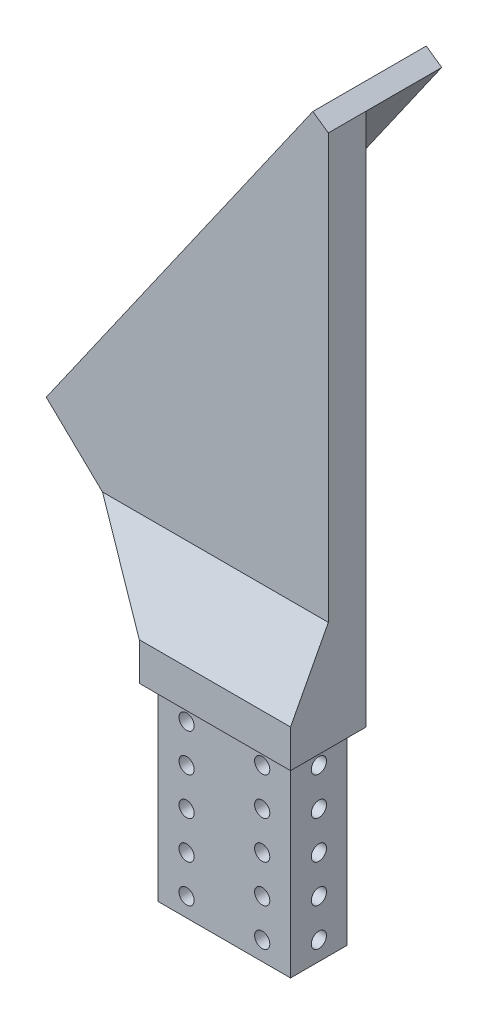
SolidWorks part; units mm, degrees
material "6061-T6 (SS)"
ref_plane "Front Plane" through (0, 0, 0) normal (0, 0, 1) x (1, 0, 0)
ref_plane "Top Plane" through (0, 0, 0) normal (0, 1, 0) x (1, 0, 0)
ref_plane "Right Plane" through (0, 0, 0) normal (1, 0, 0) x (0, 0, -1)
sketch "Sketch1" plane through (0, 0, 0) normal (0, 0, 1) x (1, 0, 0)
  line L0 (50.8, 76.2) -> (152.4, 76.2)
  line L1 (0, 0) -> (50.8, 0)
  line L2 (0, 0) -> (0, 76.2)
  line L4 (50.8, 0) -> (50.8, 76.2)
  line L5 (-101.6, 76.2) -> (0, 76.2)
  line L6 (-101.6, 76.2) -> (-101.6, 254)
  line L7 (-101.6, 254) -> (152.4, 254)
  line L8 (152.4, 76.2) -> (152.4, 254)
  dimension "D1" = 50.8
  dimension "D2" = 76.2
  dimension "D3" = 254
  dimension "D4" = 177.8
extrude "Boss-Extrude1" add sketch "Sketch1" along normal blind 25.4
sketch "Sketch3" plane through (0, 0, 25.4) normal (0, 0, 1) x (1, 0, 0)
  line L0 (50.8, 0) -> (50.8, 76.2) construction
  line L1 (0, 0) -> (50.8, 0)
  line L2 (0, 0) -> (0, 63.5)
  line L3 (0, 63.5) -> (50.8, 63.5)
  line L4 (50.8, 0) -> (50.8, 63.5)
  dimension "D1" = 63.5
sketch "Sketch4" plane through (0, 0, 0) normal (-1, 0, 0) x (0, 0, 1)
  line L0 (25.4, 0) -> (25.4, 63.5) construction
  line L1 (0, 0) -> (25.4, 0)
  line L2 (0, 0) -> (0, 63.5)
  line L3 (0, 63.5) -> (25.4, 63.5)
  line L4 (25.4, 0) -> (25.4, 63.5)
  dimension "D1" = 63.5
sketch "Sketch5" plane through (0, 0, 0) normal (0, 0, -1) x (-1, 0, 0)
  line L1 (0, 0) -> (-50.8, 0)
  line L2 (0, 0) -> (0, 63.5)
  line L3 (0, 63.5) -> (-50.8, 63.5)
  line L4 (-50.8, 0) -> (-50.8, 63.5)
sketch "Sketch6" plane through (50.8, 0, 0) normal (1, 0, 0) x (0, 0, -1)
  line L1 (0, 0) -> (-25.4, 0)
  line L2 (0, 0) -> (0, 63.5)
  line L3 (0, 63.5) -> (-25.4, 63.5)
  line L4 (-25.4, 0) -> (-25.4, 63.5)
extrude "Cut-Extrude1" cut sketch "Sketch3" against normal blind 3.175
extrude "Cut-Extrude2" cut sketch "Sketch4" against normal blind 3.175
extrude "Cut-Extrude3" cut sketch "Sketch5" against normal blind 3.175
extrude "Cut-Extrude4" cut sketch "Sketch6" against normal blind 3.175
sketch "Sketch7" plane through (0, 0, 25.4) normal (0, 0, 1) x (1, 0, 0)
  line L0 (50.8, 76.2) -> (50.8, 254)
  line L4 (152.4, 254) -> (-101.6, 254) construction
  line L5 (50.8, 76.2) -> (152.4, 76.2)
  line L6 (152.4, 76.2) -> (152.4, 254)
  line L7 (152.4, 254) -> (50.8, 254)
extrude "Cut-Extrude5" cut sketch "Sketch7" against normal through all
sketch "Sketch9" plane through (0, 0, 25.4) normal (0, 0, 1) x (1, 0, 0)
  line L0 (34.6576, 254) -> (50.8, 254)
  line L1 (50.8, 254) -> (-101.6, 254) construction
  line L2 (50.8, 254) -> (50.8, 242.697)
  line L3 (50.8, 242.697) -> (34.6576, 254)
  line L4 (50.8, 63.5) -> (50.8, 254) construction
  dimension "D1" = 11.303
  dimension "D2" = 35
extrude "Cut-Extrude7" cut sketch "Sketch9" against normal through all
sketch "Sketch8" plane through (0, 0, 25.4) normal (0, 0, 1) x (1, 0, 0)
  line L2 (34.6576, 254) -> (-101.6, 254) construction
  line L12 (34.6576, 254) -> (-101.6, 59.4039)
  line L13 (-101.6, 59.4039) -> (-101.6, 254)
  line L14 (-101.6, 254) -> (34.6576, 254)
  dimension "D1" = 55
extrude "Cut-Extrude6" cut sketch "Sketch8" against normal through all
sketch "Sketch10" plane through (0, 0, 25.4) normal (0, 0, 1) x (1, 0, 0)
  line L0 (34.6576, 254) -> (45.5977, 246.3397)
  line L1 (34.6576, 254) -> (50.8, 242.697) construction
  line L2 (45.5977, 246.3397) -> (-84.0298, 61.2124)
  line L4 (-84.0298, 61.2124) -> (-94.9699, 68.8727)
  line L5 (-94.9699, 68.8727) -> (34.6576, 254)
  line L6 (-89.8393, 76.2) -> (34.6576, 254) construction
  dimension "D1" = 13.3553
  dimension "D2" = 13.3553
  dimension "D3" = 225.9987
extrude "Cut-Extrude8" cut sketch "Sketch10" against normal through all
sketch "Sketch11" plane through (0, 0, 22.225) normal (0, 0, 1) x (1, 0, 0)
  line L1 (50.8, 63.5) -> (0, 63.5) construction
  line L2 (47.625, 63.5) -> (3.175, 63.5) construction
  line L3 (3.175, 63.5) -> (3.175, 0) construction
  circle A0 centre (12.7, 57.15) radius 2.5527
  circle A1 centre (12.7, 44.45) radius 2.5527
  circle A2 centre (12.7, 31.75) radius 2.5527
  circle A3 centre (12.7, 19.05) radius 2.5527
  circle A4 centre (12.7, 6.35) radius 2.5527
  circle A5 centre (38.1, 44.45) radius 2.5527
  circle A6 centre (38.1, 31.75) radius 2.5527
  circle A7 centre (38.1, 19.05) radius 2.5527
  circle A8 centre (38.1, 6.35) radius 2.5527
  circle A9 centre (38.1, 57.15) radius 2.5527
  dimension "D1" = 5.1054
  dimension "D2" = 9.525
  dimension "D3" = 6.35
  dimension "D6" = 25.4
  dimension "D7" = 12.7
  dimension "D8" = 6.35
  dimension "D4" = 5
  dimension "D5" = 2
sketch "Sketch12" plane through (3.175, 0, 0) normal (-1, 0, 0) x (0, 0, 1)
  line L0 (0, 63.5) -> (25.4, 63.5) construction
  line L2 (3.175, 0) -> (3.175, 63.5) construction
  circle A0 centre (12.7, 57.15) radius 2.5527
  circle A1 centre (12.7, 44.45) radius 2.5527
  circle A2 centre (12.7, 31.75) radius 2.5527
  circle A3 centre (12.7, 19.05) radius 2.5527
  circle A4 centre (12.7, 6.35) radius 2.5527
  dimension "D1" = 6.35
  dimension "D2" = 9.525
  dimension "D3" = 5.1054
  dimension "D5" = 12.7
  dimension "D4" = 5
extrude "Cut-Extrude9" cut sketch "Sketch11" against normal through all
extrude "Cut-Extrude10" cut sketch "Sketch12" against normal through all
sketch "Sketch17" plane through (0, 0, 0) normal (0, 0, -1) x (-1, 0, 0)
  line L0 (-45.5977, 246.3397) -> (-50.7993, 242.6975)
  line L1 (-45.5977, 246.3397) -> (-50.8, 242.697) construction
  line L2 (-50.7993, 242.6975) -> (68.988, 71.6236)
  line L3 (68.988, 71.6236) -> (74.1896, 75.2658)
  line L4 (74.1896, 75.2658) -> (-45.5977, 246.3397)
  dimension "D1" = 6.35
extrude "Boss-Extrude2" add sketch "Sketch17" along normal blind 25.4
sketch "Sketch18" plane through (0, 0, -25.4) normal (0, 0, -1) x (-1, 0, 0)
  line L0 (65.7835, 76.2) -> (73.5354, 76.2)
  line L1 (73.5354, 76.2) -> (74.1896, 75.2658)
  line L2 (74.1896, 75.2658) -> (68.988, 71.6236)
  line L3 (68.988, 71.6236) -> (65.7835, 76.2)
extrude "Cut-Extrude11" cut sketch "Sketch18" against normal through all
sketch "Sketch19" plane through (0, 0, 25.4) normal (0, 0, 1) x (1, 0, 0)
  line L0 (0, 76.2) -> (-43.9727, 118.4199)
  line L1 (-73.5354, 76.2) -> (0, 76.2) construction
  line L2 (-73.5354, 76.2) -> (45.5977, 246.3397) construction
  line L3 (-43.9727, 118.4199) -> (-73.5354, 76.2)
  line L4 (-73.5354, 76.2) -> (0, 76.2)
  dimension "D1" = 60.96
extrude "Cut-Extrude12" cut sketch "Sketch19" against normal through all
sketch "Sketch20" plane through (50.8, 0, 0) normal (1, 0, 0) x (0, 0, -1)
  line L0 (-25.4, 76.2) -> (-12.7, 100.2897)
  line L1 (-25.4, 63.5) -> (-25.4, 242.697) construction
  line L2 (-12.7, 100.2897) -> (-12.7, 246.3397)
  line L3 (25.4, 246.3397) -> (-25.4, 246.3397) construction
  line L4 (-12.7, 246.3397) -> (-25.4, 246.3397)
  line L5 (-25.4, 246.3397) -> (-25.4, 76.2)
  dimension "D1" = 12.7
  dimension "D2" = 146.05
  dimension "D3" = 12.7
extrude "Cut-Extrude13" cut sketch "Sketch20" against normal through all
